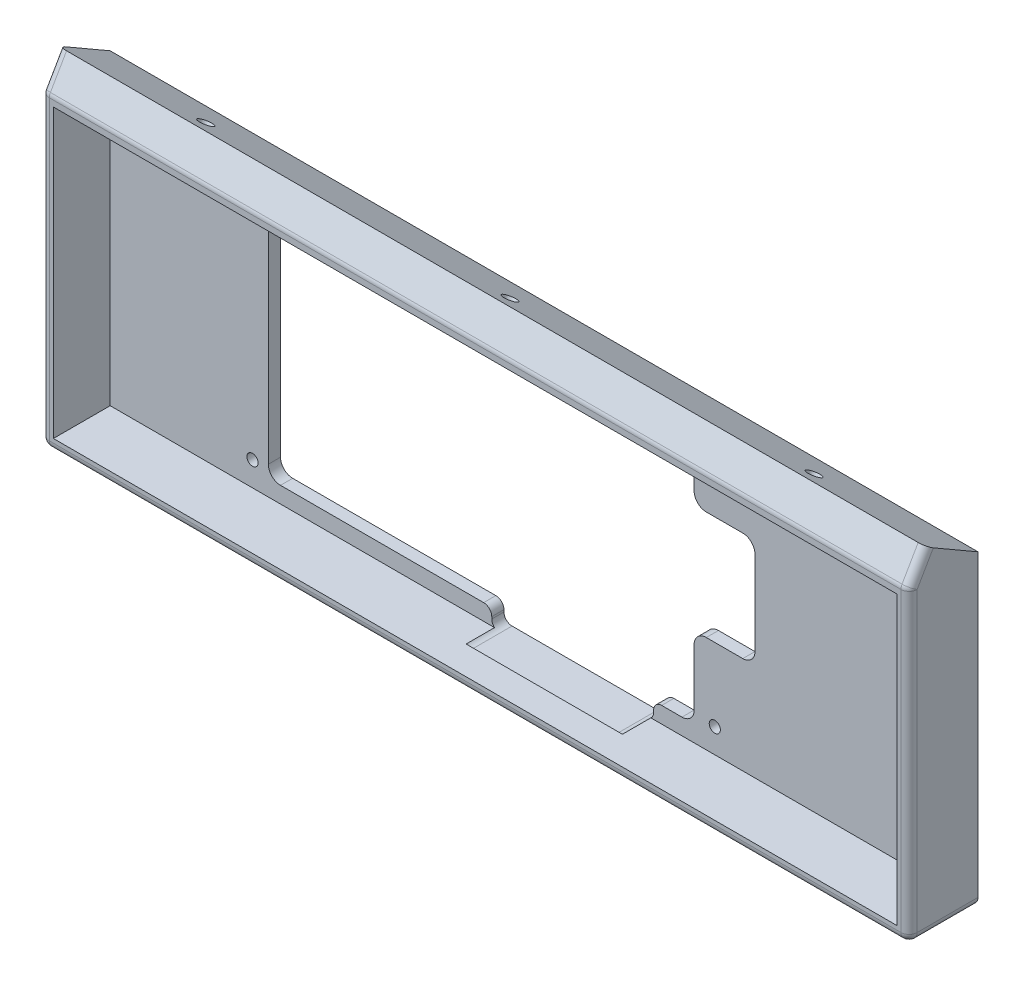
SolidWorks part; units mm, degrees
ref_plane "Front Plane" through (0, 0, 0) normal (0, 0, 1) x (1, 0, 0)
ref_plane "Top Plane" through (0, 0, 0) normal (0, 1, 0) x (1, 0, 0)
ref_plane "Right Plane" through (0, 0, 0) normal (1, 0, 0) x (0, 0, -1)
sketch "Sketch1" plane through (0, 0, 0) normal (0, 0, 1) x (1, 0, 0)
  line L1 (359.7057, -1286.7739) -> (573.7057, -1286.7739)
  line L2 (359.7057, -1286.7739) -> (359.7057, -1362.5739)
  line L3 (359.7057, -1362.5739) -> (573.7057, -1362.5739)
  line L4 (573.7057, -1286.7739) -> (573.7057, -1362.5739)
  line L5 (359.7057, -1286.7739) -> (573.7057, -1362.5739) construction
  line L6 (359.7057, -1362.5739) -> (573.7057, -1286.7739) construction
  point P0 (0, 0)
  dimension "D1" = 214
  dimension "D2" = 75.8
extrude "Boss-Extrude1" add sketch "Sketch1" along normal blind 17
sketch "Sketch6" plane through (573.7057, 0, 0) normal (1, 0, 0) x (0, 0, -1)
  line L0 (-17, -1286.7739) -> (-12.75, -1279.4127)
  line L1 (-12.75, -1279.4127) -> (0, -1286.7739)
  line L2 (0, -1286.7739) -> (-17, -1286.7739)
  dimension "D1" = 60
  dimension "D2" = 90
extrude "BossExtention" add sketch "Sketch6" against normal up to surface (214 mm away) up to face at (359.7057, -1324.6739, 8.5)
shell "Shellit" thickness 3 removed face at (466.7057, -1324.6739, 17)
sketch "Sketch7" plane through (0, 0, 17) normal (0, 0, 1) x (1, 0, 0)
  line L2 (362.7057, -1292.7739) -> (362.7057, -1288.7739)
  line L3 (362.7057, -1288.7739) -> (570.7057, -1288.7739)
  line L4 (570.7057, -1292.7739) -> (570.7057, -1288.7739)
  line L6 (362.7057, -1292.7739) -> (570.7057, -1292.7739)
  line L8 (362.7057, -1292.7739) -> (362.7057, -1283.5108) construction
  point P4 (-0.006, 33.4001)
  dimension "D1" = 4
extrude "Cut-Extrude4" cut sketch "Sketch7" against normal blind 3
sketch "Sketch3" plane through (0, 0, 3) normal (0, 0, 1) x (1, 0, 0)
  line L3 (397.8057, -1294.4739) -> (511.8057, -1294.4739) construction
  line L4 (511.8057, -1294.4739) -> (511.8057, -1353.5739) construction
  line L5 (511.8057, -1353.5739) -> (397.8057, -1353.5739) construction
  line L6 (397.8057, -1353.5739) -> (397.8057, -1294.4739) construction
  line L7 (362.7057, -1359.5739) -> (570.7057, -1359.5739) construction
  line L8 (362.7057, -1288.7739) -> (362.7057, -1359.5739) construction
  line L9 (570.7057, -1359.5739) -> (570.7057, -1288.7739) construction
  circle A0 centre (397.8057, -1294.4739) radius 1.375
  circle A1 centre (511.8057, -1294.4739) radius 1.375
  circle A2 centre (397.8057, -1353.5739) radius 1.375
  circle A3 centre (511.8057, -1353.5739) radius 1.375
  dimension "D1" = 2.75
  dimension "D2" = 59.1
  dimension "D3" = 6
  dimension "D4" = 35.1
  dimension "D5" = 58.9
extrude "Mounting Holes" cut sketch "Sketch3" against normal through all
sketch "Sketch4" plane through (0, 0, 0) normal (0, 0, -1) x (-1, 0, 0)
  line L0 (-359.7057, -1362.5739) -> (-573.7057, -1362.5739) construction
  line L1 (-404.7057, -1355.5739) -> (-454.8057, -1355.5739)
  line L2 (-401.7057, -1352.5739) -> (-401.7057, -1295.7739)
  line L3 (-404.7057, -1292.7739) -> (-503.7057, -1292.7739)
  line L5 (-401.7057, -1355.5739) -> (-503.7057, -1292.7739) construction
  line L6 (-401.7057, -1292.7739) -> (-503.7057, -1355.5739) construction
  line L9 (-506.7057, -1295.7739) -> (-506.7057, -1305.7739)
  line L17 (-359.7057, -1286.7739) -> (-359.7057, -1362.5739) construction
  line L18 (-573.7057, -1362.5739) -> (-573.7057, -1286.7739) construction
  line L19 (-573.7057, -1286.7739) -> (-359.7057, -1286.7739) construction
  line L20 (-496.7057, -1357.5739) -> (-496.7057, -1358.0739)
  line L21 (-494.7057, -1360.0739) -> (-458.8057, -1360.0739)
  line L22 (-456.8057, -1358.0739) -> (-456.8057, -1357.5739)
  line L23 (-498.7057, -1355.5739) -> (-503.7057, -1355.5739)
  line L27 (-509.7057, -1308.7739) -> (-518.7057, -1308.7739)
  line L28 (-521.7057, -1311.7739) -> (-521.7057, -1332.5739)
  line L29 (-518.7057, -1335.5739) -> (-509.7057, -1335.5739)
  line L30 (-506.7057, -1338.5739) -> (-506.7057, -1352.5739)
  arc A0 (-503.7057, -1355.5739) -> (-506.7057, -1352.5739) centre (-503.7057, -1352.5739) cw
  arc A2 (-404.7057, -1292.7739) -> (-401.7057, -1295.7739) centre (-404.7057, -1295.7739) cw
  arc A5 (-401.7057, -1352.5739) -> (-404.7057, -1355.5739) centre (-404.7057, -1352.5739) cw
  arc A14 (-506.7057, -1295.7739) -> (-503.7057, -1292.7739) centre (-503.7057, -1295.7739) cw
  arc A16 (-494.7057, -1360.0739) -> (-496.7057, -1358.0739) centre (-494.7057, -1358.0739) cw
  arc A17 (-458.8057, -1360.0739) -> (-456.8057, -1358.0739) centre (-458.8057, -1358.0739) ccw
  arc A18 (-496.7057, -1357.5739) -> (-498.7057, -1355.5739) centre (-498.7057, -1357.5739) ccw
  arc A19 (-456.8057, -1357.5739) -> (-454.8057, -1355.5739) centre (-454.8057, -1357.5739) cw
  arc A20 (-509.7057, -1308.7739) -> (-506.7057, -1305.7739) centre (-509.7057, -1305.7739) ccw
  arc A21 (-506.7057, -1338.5739) -> (-509.7057, -1335.5739) centre (-509.7057, -1338.5739) ccw
  arc A22 (-521.7057, -1332.5739) -> (-518.7057, -1335.5739) centre (-518.7057, -1332.5739) ccw
  arc A23 (-521.7057, -1311.7739) -> (-518.7057, -1308.7739) centre (-518.7057, -1311.7739) cw
  point P4 (-452.7057, -1324.1739)
  point P39 (-496.7057, -1355.5739)
  point P51 (-506.7057, -1335.5739)
  dimension "D5" = 3
  dimension "D6" = 3
  dimension "D7" = 4.5
  dimension "D11" = 3
  dimension "D15" = 15
  dimension "D3" = 3
  dimension "D10" = 2
  dimension "D12" = 3
  dimension "D1" = 67
  dimension "D2" = 7
  dimension "D4" = 6
  dimension "D8" = 55.1
  dimension "D9" = 10
  dimension "D13" = 16
  dimension "D14" = 20
  dimension "D16" = 22
  dimension "D20" = 42
extrude "PI_Hole" cut sketch "Sketch4" against normal blind 8
chamfer "Chamfer1" distance 2 angle 45 1 edges at (476.7557, -1359.5739, 8)
fillet "Fillet1" radius 2 8 edges at (466.7057, -1362.5739, 17) (359.7057, -1324.6739, 17) (573.7057, -1324.6739, 17) (573.7057, -1362.5739, 8.5) (359.7057, -1362.5739, 8.5) (466.7057, -1286.7739, 17) (359.7057, -1283.0933, 14.875) (573.7057, -1283.0933, 14.875)
sketch "Sketch11" plane through (0, -967.6785, 558.6894) normal (0, -0.866, 0.5) x (1, 0, 0)
  line L0 (381.555, -633.6645) -> (556.7386, -633.6645) construction
  line L1 (466.7057, -628.9325) -> (466.7057, -639.4538) construction
  line L2 (571.7057, -628.9325) -> (361.7057, -628.9325) construction
  line L3 (361.7057, -628.6645) -> (571.7057, -628.6645) construction
  line L5 (549.1219, -633.6645) -> (567.7057, -633.6645) construction
  circle A0 centre (466.7057, -633.6645) radius 1.7
  circle A1 centre (541.7057, -633.6645) radius 1.7
  circle A2 centre (391.7057, -633.6645) radius 1.7
  dimension "D1" = 3.4
  dimension "D3" = 75
  dimension "D4" = 75
  dimension "D2" = 5
extrude "Cut-Extrude5" cut sketch "Sketch11" against normal through all
sketch "Sketch12" plane through (0, -967.6785, 558.6894) normal (0, -0.866, 0.5) x (1, 0, 0)
  circle A0 centre (391.7057, -633.6645) radius 2.75
  circle A1 centre (466.7057, -633.6645) radius 2.75
  circle A2 centre (541.7057, -633.6645) radius 2.75
  dimension "D1" = 5.5
extrude "Cut-Extrude6" cut sketch "Sketch12" against normal blind 1 and the other way through all
